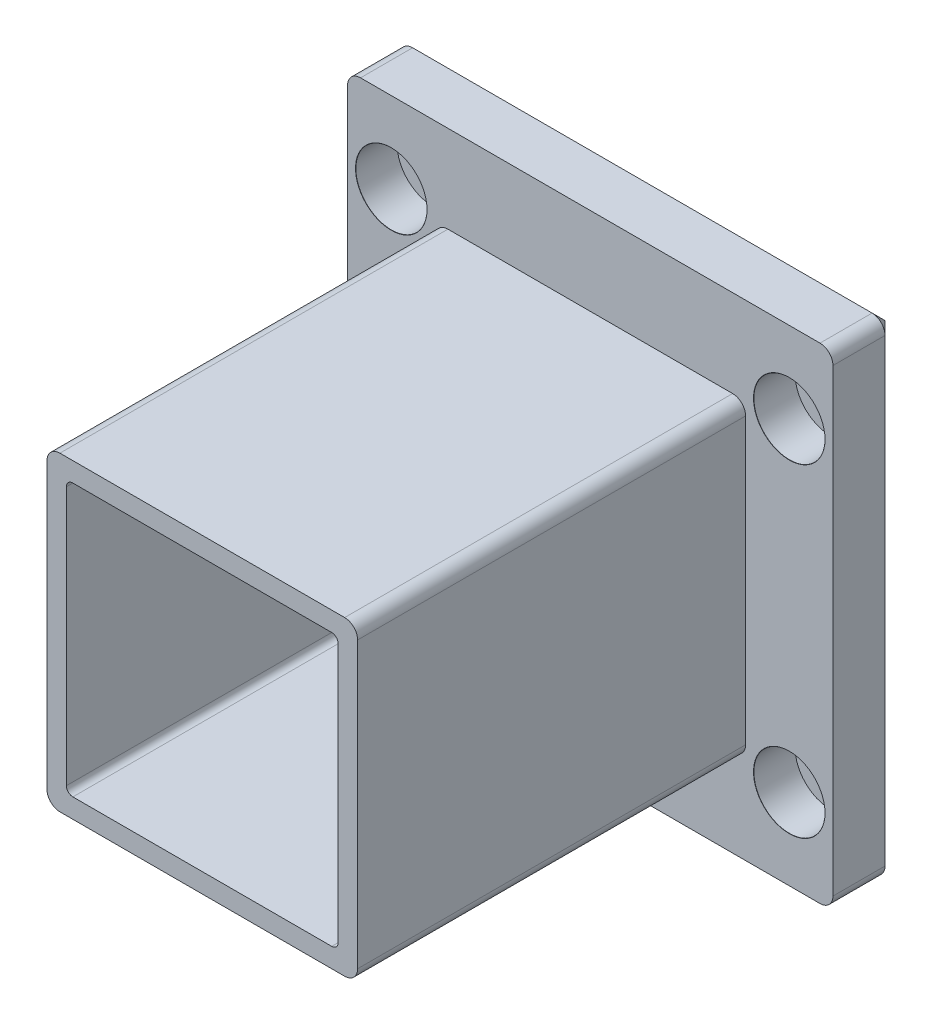
SolidWorks part; units mm, degrees
ref_plane "Front Plane" through (0, 0, 0) normal (1, 0, 0) x (0, 1, 0)
ref_plane "Top Plane" through (0, 0, 0) normal (0, 0, 1) x (0, 1, 0)
ref_plane "Right Plane" through (0, 0, 0) normal (0, 1, 0) x (-1, 0, 0)
sketch "Sketch1" plane through (0, 0, 0) normal (0, 0, 1) x (0, 1, 0)
  line L0 (-25.048, 30.1461) -> (-26.1566, 30.1461)
  line L1 (-25.048, 30.1461) -> (22.952, 30.1461)
  line L2 (-25.048, 30.1461) -> (-25.048, -17.8539)
  line L3 (-25.048, -17.8539) -> (22.952, -17.8539)
  line L4 (22.952, 30.1461) -> (22.952, -17.8539)
  line L6 (22.952, 30.1461) -> (15.3397, 30.1461)
  line L8 (-22.048, 27.1461) -> (-22.048, -14.8539)
  line L9 (-22.048, -14.8539) -> (19.952, -14.8539)
  line L10 (19.952, 27.1461) -> (19.952, -14.8539)
  line L11 (-22.048, 27.1461) -> (19.952, 27.1461)
  dimension "D1" = 42
  dimension "D2" = 42
  dimension "D3" = 3
extrude "Boss-Extrude1" add sketch "Sketch1" along normal blind 65 contours L4 L1 L0 L2 L3 L8 L11 L10 L9 region at (-29.4673, -4.8542, 0)
sketch "Sketch3" plane through (0, 0, 0) normal (0, 0, -1) x (1, 0, 0)
  line L0 (-6.1461, 25.048) -> (-6.1461, -22.952)
  line L1 (-30.1461, 25.048) -> (17.8539, 25.048) construction
  line L2 (-30.1461, -22.952) -> (17.8539, -22.952) construction
  line L3 (17.8539, 25.048) -> (31.3539, 38.548)
  line L4 (-43.6461, 38.548) -> (31.3539, 38.548)
  line L5 (-43.6461, 38.548) -> (-43.6461, -36.452)
  line L6 (-43.6461, -36.452) -> (31.3539, -36.452)
  line L7 (31.3539, 38.548) -> (31.3539, -36.452)
  line L8 (-43.6461, 38.548) -> (31.3539, -36.452) construction
  line L9 (-43.6461, -36.452) -> (31.3539, 38.548) construction
  line L10 (24.6039, -23.952) -> (24.6039, 26.048)
  line L11 (24.6039, -29.702) -> (24.6039, 31.798)
  line L12 (-31.1461, 31.798) -> (18.8539, 31.798)
  line L13 (-36.8961, -23.952) -> (-36.8961, 26.048)
  line L14 (18.8539, -29.702) -> (-31.1461, -29.702)
  point P6 (-6.1461, 1.048)
  point P22 (24.6039, 1.048)
  line M5 (-30.1461, -22.952) -> (17.8539, -22.952)
  line M6 (17.8539, -22.952) -> (17.8539, 25.048)
  line M7 (17.8539, 25.048) -> (-30.1461, 25.048)
  line M9 (-27.1461, 22.048) -> (14.8539, 22.048)
  line M10 (14.8539, 22.048) -> (14.8539, -19.952)
  line M11 (14.8539, -19.952) -> (-27.1461, -19.952)
  line M12 (-27.1461, -19.952) -> (-27.1461, 22.048)
  dimension "D1" = 50
  dimension "D2" = 75
extrude "Boss-Extrude2" add sketch "Sketch3" along normal blind 5 contours L0 M9 M12 M11 | L0 M9 M11 M10 | L0 M7 M5 M11 M12 M9 | L0 M7 M9 M10 M11 M5 M6 | L7 L4 L5 L6 M5 M7 M6 | L5 L4 L7 L6 region at (5.8539, -24.5113, 0) region at (30.2932, -1.048, 0) region at (4.3539, -1.048, 0) region at (-16.6461, -1.048, 0)
sketch "Sketch8" plane through (0, 0, 0) normal (0, 0, 1) x (1, 0, 0)
  line L1 (-43.6461, 36.452) -> (31.3539, 36.452)
  line L2 (-43.6461, 36.452) -> (-43.6461, -38.548)
  line L3 (-43.6461, -38.548) -> (31.3539, -38.548)
  line L4 (31.3539, 36.452) -> (31.3539, -38.548)
  line L5 (-27.1461, 19.952) -> (14.8539, 19.952)
  line L6 (-27.1461, 19.952) -> (-27.1461, -22.048)
  line L7 (-27.1461, -22.048) -> (14.8539, -22.048)
  line L8 (14.8539, 19.952) -> (14.8539, -22.048)
extrude "Boss-Extrude3" add sketch "Sketch8" along normal blind 5.0471
fillet "Fillet1" radius 2 8 edges at (17.8539, -25.048, 35.0235) (17.8539, 22.952, 35.0235) (31.3539, 36.452, 0.0235) (-43.6461, 36.452, 0.0235) (-43.6461, -38.548, 0.0235) (31.3539, -38.548, 0.0235) (-30.1461, 22.952, 35.0235) (-30.1461, -25.048, 35.0235)
sketch "Sketch13" plane through (0, 0, 5.0471) normal (0, 0, 1) x (1, 0, 0)
  line L0 (-36.8961, 23.952) -> (-36.8961, -26.048)
  line L1 (-31.1461, -31.798) -> (18.8539, -31.798)
  line L2 (-43.6461, 36.452) -> (31.3539, -38.548)
  line L3 (24.6039, 23.952) -> (24.6039, -26.048)
  line L4 (-31.1461, 29.702) -> (18.8539, 29.702)
  point P0 (-36.8961, 23.952)
  point P1 (-36.8961, -26.048)
  point P12 (24.6039, 23.952)
  point P13 (24.6039, -26.048)
hole_wizard "CBORE for M6 Hex Socket Head Cap Screw2" positions "Sketch13" profile "Sketch15" counterbore size "M6" standard "ISO" end condition through all
sketch "Sketch15" plane through (-36.8961, 23.952, 5.0471) normal (1, 0, 0) x (0, -1, 0)
  line L0 (0, 0) -> (0, 10.0471)
  line L1 (0, 10.0471) -> (3.3, 10.0471)
  line L3 (3.3, 10.0471) -> (3.3, 6.4)
  line L4 (5.5, 6.4) -> (3.3, 6.4)
  line L5 (5.5, 6.4) -> (5.5, 0.025)
  line L6 (5.5, 0.025) -> (5.525, 0)
  line L7 (5.525, 0) -> (0, 0)
  line L8 (-5.5, 0.025) -> (-5.525, 0) construction
  line L11 (0, -6.35) -> (0, 107.95) construction
  dimension "Thru Hole Dia." = 6.6
  dimension "Thru Hole Depth" = 10.0471
  dimension "C'Bore Dia." = 11
  dimension "C'Bore Depth" = 6.4
  dimension "Near C'Sink Dia." = 11.05
  dimension "Near C'Sink Angle" = 90
fillet "Fillet2" radius 1 4 edges at (14.8539, -22.048, 32.5) (14.8539, 19.952, 32.5) (-27.1461, 19.952, 32.5) (-27.1461, -22.048, 32.5)
chamfer "Chamfer1" distance 2 angle 45 8 edges at (-43.6461, -1.048, -5) (-6.1461, -38.548, -5) (-6.1461, 36.452, -5) (-43.0603, -37.9622, -5) (-43.0603, 35.8662, -5) (30.7681, -37.9622, -5) (30.7681, 35.8662, -5) (31.3539, -1.048, -5)
